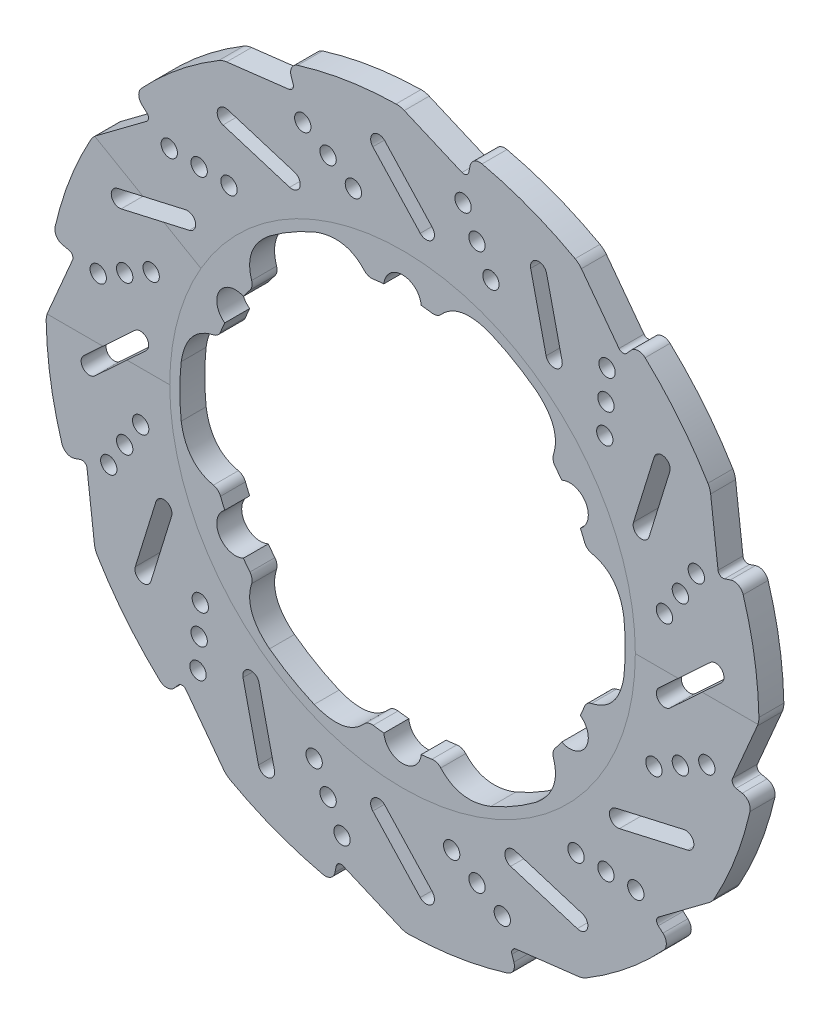
SolidWorks part; units mm, degrees
ref_plane "Front Plane" through (0, 0, 0) normal (0, 0, 1) x (1, 0, 0)
ref_plane "Top Plane" through (0, 0, 0) normal (0, 1, 0) x (1, 0, 0)
ref_plane "Right Plane" through (0, 0, 0) normal (1, 0, 0) x (0, 0, -1)
sketch "Sketch1" plane through (0, 0, 0) normal (0, 0, 1) x (1, 0, 0)
  circle A0 centre (0, 0) radius 90.805
  circle A1 centre (0, 0) radius 56.769
  dimension "D1" = 181.61
  dimension "D2" = 34.036
extrude "RotorBody" add sketch "Sketch1" along normal blind 6.35
sketch "Sketch2" plane through (0, 0, 6.35) normal (0, 0, 1) x (1, 0, 0)
  line L0 (0, 49.149) -> (0, 56.6) construction
  circle A0 centre (0, 0) radius 49.149 construction
  circle A1 centre (0, 49.149) radius 4.7625
  circle A2 centre (0, 0) radius 49.784
  circle A4 centre (0, 0) radius 56.769 construction
  spline S0 degree 2 poles (-8.89, 48.9838) (-14.5829, 56.567) (-25.4, 50.7697) knots 0 0 0 1 1 1
  spline S1 degree 2 poles (8.89, 48.9838) (14.5829, 56.567) (25.4, 50.7697) knots 0 0 0 1 1 1
  circle M2 centre (0, 0) radius 56.769
  dimension "D1" = 98.298
  dimension "D2" = 9.525
  dimension "D4" = 8.89
  dimension "D5" = 11.43
  dimension "D6" = 25.4
  dimension "D7" = 2.54
  dimension "D3" = 0.635
extrude "FloatPinIF" add sketch "Sketch2" against normal through all contours A2 S1 S0 A1 M2 region at (0, 54.3683, 6.35)
pattern_circular "FloatPinPattern" count 6 over 360 about axis through (0, 0, 6.35) along (0, 0, -1) of "FloatPinIF" reverse direction yes
sketch "Sketch3" plane through (0, 0, 6.35) normal (0, 0, 1) x (1, 0, 0)
  line L0 (-6.0411, 79.801) -> (6.0411, 66.757) construction
  line L1 (-6.0411, 79.801) -> (0, 0) construction
  line L2 (0, 0) -> (6.0411, 66.757) construction
  line L3 (-7.5691, 78.3857) -> (4.5131, 65.3416)
  line L4 (-4.5131, 81.2164) -> (7.5691, 68.1723)
  line L5 (15.4112, 77.5221) -> (22.5208, 64.042) construction
  line L6 (34.6688, 72.1303) -> (38.6102, 54.7927) construction
  line L7 (52.1562, 60.6996) -> (51.476, 42.9326) construction
  line L8 (66.0892, 45.1323) -> (60.8338, 28.1467) construction
  line L9 (75.5183, 26.4893) -> (66.0458, 11.4427) construction
  line L10 (79.801, 6.0411) -> (66.757, -6.0411) construction
  line L11 (78.6454, -14.8188) -> (62.9187, -23.1132) construction
  line L12 (72.1303, -34.6688) -> (54.7927, -38.6102) construction
  line L13 (60.6996, -52.1562) -> (42.9326, -51.476) construction
  line L14 (45.1323, -66.0892) -> (28.1467, -60.8338) construction
  line L15 (26.4893, -75.5183) -> (11.4427, -66.0458) construction
  line L16 (6.0411, -79.801) -> (-6.0411, -66.757) construction
  line L17 (-14.8188, -78.6454) -> (-23.1132, -62.9187) construction
  line L18 (-34.6688, -72.1303) -> (-38.6102, -54.7927) construction
  line L19 (-52.1562, -60.6996) -> (-51.476, -42.9326) construction
  line L20 (-66.0892, -45.1323) -> (-60.8338, -28.1467) construction
  line L21 (-75.5183, -26.4893) -> (-66.0458, -11.4427) construction
  line L22 (-79.801, -6.0411) -> (-66.757, 6.0411) construction
  line L23 (-78.6454, 14.8188) -> (-62.9187, 23.1132) construction
  line L24 (-72.1303, 34.6688) -> (-54.7927, 38.6102) construction
  line L25 (-60.6996, 52.1562) -> (-42.9326, 51.476) construction
  line L26 (-45.1323, 66.0892) -> (-28.1467, 60.8338) construction
  line L27 (-26.4893, 75.5183) -> (-11.4427, 66.0458) construction
  line L28 (18.966, 70.7821) -> (0, 0) construction
  line L29 (0, 0) -> (0, 73.279) construction
  circle A0 centre (0, 0) radius 59.309
  circle A1 centre (0, 0) radius 90.805 construction
  circle A2 centre (0, 0) radius 73.279 construction
  arc A3 (-7.5691, 78.3857) -> (-4.5131, 81.2164) centre (-6.0411, 79.801) cw
  arc A4 (4.5131, 65.3416) -> (7.5691, 68.1723) centre (6.0411, 66.757) ccw
  circle A5 centre (15.4112, 77.5221) radius 2.0828
  circle A6 centre (22.5208, 64.042) radius 2.0828
  circle A7 centre (18.966, 70.7821) radius 2.0828
  point P8 (0, 73.279)
  point P64 (0, 0)
  dimension "D1" = 31.496
  dimension "D2" = 13.97
  dimension "D8" = 4.1656
  dimension "D9" = 4.1656
  dimension "D10" = 4.1656
  dimension "D3" = 17.78
  dimension "D4" = 9.5
  dimension "D11" = 15
  dimension "D7" = 15.24
  dimension "D5" = 2.0828
  dimension "D6" = 2.0828
extrude "Slot+Holes" cut sketch "Sketch3" against normal through all contours A5 | A7 | A6 | L3 A4 L4 A3 region at (15.4112, 77.5221, 6.35) region at (22.5208, 64.042, 6.35) region at (18.966, 70.7821, 6.35)
pattern_circular "Slot+HolesPattern" count 12 over 360 about axis through (0, 0, 6.35) along (0, 0, -1) of "Slot+Holes" reverse direction yes
sketch "Sketch5" plane through (0, 0, 6.35) normal (0, 0, 1) x (1, 0, 0)
  line L0 (-25.4145, 74.8417) -> (-12.5175, 66.7224) construction
  line L3 (4.5589, 60.4742) -> (-38.4313, 87.5385)
  line L4 (4.5589, 60.4742) -> (0.4993, 54.0256)
  line L5 (-38.4313, 87.5385) -> (-42.491, 81.09)
  line L6 (0.4993, 54.0256) -> (-42.491, 81.09)
  line L7 (4.5589, 60.4742) -> (-42.491, 81.09) construction
  line L8 (-38.4313, 87.5385) -> (0.4993, 54.0256) construction
  line L19 (17.7025, 89.0627) -> (0, 0)
  line L20 (15.4112, 77.5221) -> (22.5208, 64.042) construction
  line L29 (44.9285, 78.9112) -> (56.0946, 63.9821)
  line L30 (0, 0) -> (16.5883, 83.4574) construction
  line L31 (10.4868, 95.0262) -> (34.1853, 50.0927) construction
  line L32 (10.4868, 95.0262) -> (3.7467, 91.4715)
  line L33 (34.1853, 50.0927) -> (27.4452, 46.5379)
  line L34 (3.7467, 91.4715) -> (27.4452, 46.5379) construction
  line L35 (10.4868, 95.0262) -> (27.4452, 46.5379) construction
  line L36 (34.1853, 50.0927) -> (3.7467, 91.4715) construction
  line L37 (-29.2006, 85.9818) -> (0, 0)
  line L38 (-0.5464, 90.8034) -> (16.5883, 83.4574)
  line L39 (7.4565, 65.2289) -> (-15.0676, 89.5462) construction
  arc A1 (16.8939, 84.9946) -> (15.1478, 84.075) centre (15.6482, 85.2422) cw
  circle A2 centre (0, 0) radius 85.09
  circle A3 centre (0, 0) radius 90.805 construction
  circle A4 centre (0, 0) radius 90.805
  arc A5 (17.2002, 86.5356) -> (20.2581, 88.5164) centre (19.6914, 86.0404) cw
  arc A6 (-1.6526, 90.79) -> (0.4415, 90.3798) centre (-1.5602, 85.7108) cw
  arc A7 (4.5131, 65.3416) -> (7.5691, 68.1723) centre (6.0411, 66.757) ccw construction
  point P16 (18.966, 70.7821)
  point P17 (-18.966, 70.7821)
  point P24 (-18.966, 70.7821)
  point P29 (0, 0)
  point P38 (16.5883, 83.4574)
  point P43 (18.966, 70.7821)
  point P49 (-27.3628, 80.5704)
  dimension "D6" = 50.8
  dimension "D7" = 170.18
  dimension "D3" = 181.61
  dimension "D10" = 2.54
  dimension "D11" = 1.27
  dimension "D12" = 5.08
  dimension "D1" = 7.62
  dimension "D2" = 7.62
  dimension "D4" = 50.8
  dimension "D5" = 2
  dimension "D8" = 14.5755
  dimension "D9" = 85.09
  dimension "D13" = 14.5755
extrude "PerimeterCutOut" cut sketch "Sketch5" against normal through all contours L19 A4 L38 region at (10.936, 88.0437, 6.35)
pattern_circular "PerimeterPattern" count 12 over 360 about axis through (0, 0, 6.35) along (0, 0, -1) of "PerimeterCutOut"
extrude "PerimeterFillet" cut sketch "Sketch5<5>" against normal through all contours L19 A5 A4 | A4 A6 L38 region at (-0.5717, 90.7166, 6.35) region at (18.1631, 88.3812, 6.35)
sketch "Sketch5<5>" plane through (0, 0, 6.35) normal (0, 0, 1) x (1, 0, 0) same geometry as "Sketch5"
pattern_circular "PFilletPattern" count 12 over 360 about axis through (0, 0, 6.35) along (0, 0, -1) of "PerimeterFillet" reverse direction yes
fillet "FloatPinIFFillets" radius 2.54 12 edges at (37.9762, 32.1909, 3.175) (46.8662, 16.7929, 3.175) (46.8662, -16.7929, 3.175) (37.9762, -32.1909, 3.175) (8.89, -48.9838, 3.175) (-8.89, -48.9838, 3.175) (-37.9762, -32.1909, 3.175) (-46.8662, -16.7929, 3.175) (-46.8662, 16.7929, 3.175) (-37.9762, 32.1909, 3.175) (8.89, 48.9838, 3.175) (-8.89, 48.9838, 3.175)
sketch "Sketch6" plane through (0, 0, 6.35) normal (0, 0, 1) x (1, 0, 0)
  line L0 (-90.805, 0) -> (-59.309, 0)
  line L1 (0, 0) -> (-51.3631, 29.6545) construction
  line L2 (-59.309, 0) -> (59.309, 0) construction
  line L3 (59.309, 0) -> (90.805, 0)
  line L4 (-51.3631, 29.6545) -> (-78.6394, 45.4025)
  circle A0 centre (0, 0) radius 59.309
  circle A1 centre (0, 0) radius 90.805
  point P8 (59.309, 0)
  point P9 (-51.3631, 29.6545)
  point P10 (-59.309, 0)
  dimension "D1" = 181.61
  dimension "D2" = 31.496
  dimension "D3" = 150
split line "SplitLine"
